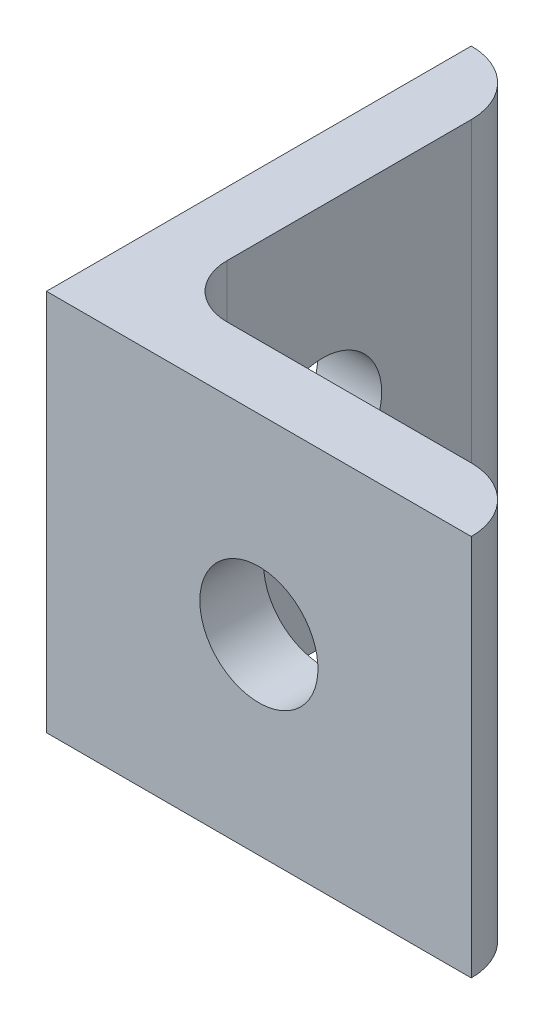
SolidWorks part; units mm, degrees
ref_plane "Front Plane" through (0, 0, 0) normal (0, 0, 1) x (1, 0, 0)
ref_plane "Top Plane" through (0, 0, 0) normal (0, 1, 0) x (1, 0, 0)
ref_plane "Right Plane" through (0, 0, 0) normal (1, 0, 0) x (0, 0, -1)
sketch "Sketch1" plane through (0, 0, 0) normal (0, 1, 0) x (1, 0, 0)
  line L0 (0, 0) -> (0, 20)
  line L1 (0, 0) -> (20, 0)
  line L3 (3, 17) -> (3, 5.5)
  line L4 (5.5, 3) -> (17, 3)
  line L6 (0, 20) -> (20, 20) construction
  line L7 (20, 0) -> (20, 20) construction
  arc A0 (0, 20) -> (3, 17) centre (0, 17) cw
  arc A1 (20, 0) -> (17, 3) centre (17, 0) ccw
  arc A2 (5.5, 3) -> (3, 5.5) centre (5.5, 5.5) cw
  dimension "D3" = 3
  dimension "D4" = 2.5
  dimension "D1" = 20
  dimension "D2" = 3
extrude "Boss-Extrude1" add sketch "Sketch1" along normal mid plane 18
sketch "Sketch2" plane through (0, 0, -3) normal (0, 0, -1) x (-1, 0, 0)
  line L0 (-17, 9) -> (-5.5, 9) construction
  line L2 (0, 9) -> (0, -9) construction
  circle A0 centre (-10, 0) radius 2.78
  dimension "D1" = 5.56
  dimension "D2" = 9
  dimension "D3" = 10
extrude "Cut-Extrude1" cut sketch "Sketch2" against normal through all
sketch "Sketch3" plane through (3, 0, 0) normal (1, 0, 0) x (0, 0, -1)
  line L1 (20, 9) -> (20, -9) construction
  line L2 (0, 9) -> (0, -9) construction
  circle A0 centre (10, 0) radius 2.78
  point P7 (20, 0)
  dimension "D1" = 10
  dimension "D2" = 5.56
extrude "Cut-Extrude2" cut sketch "Sketch3" against normal through all
